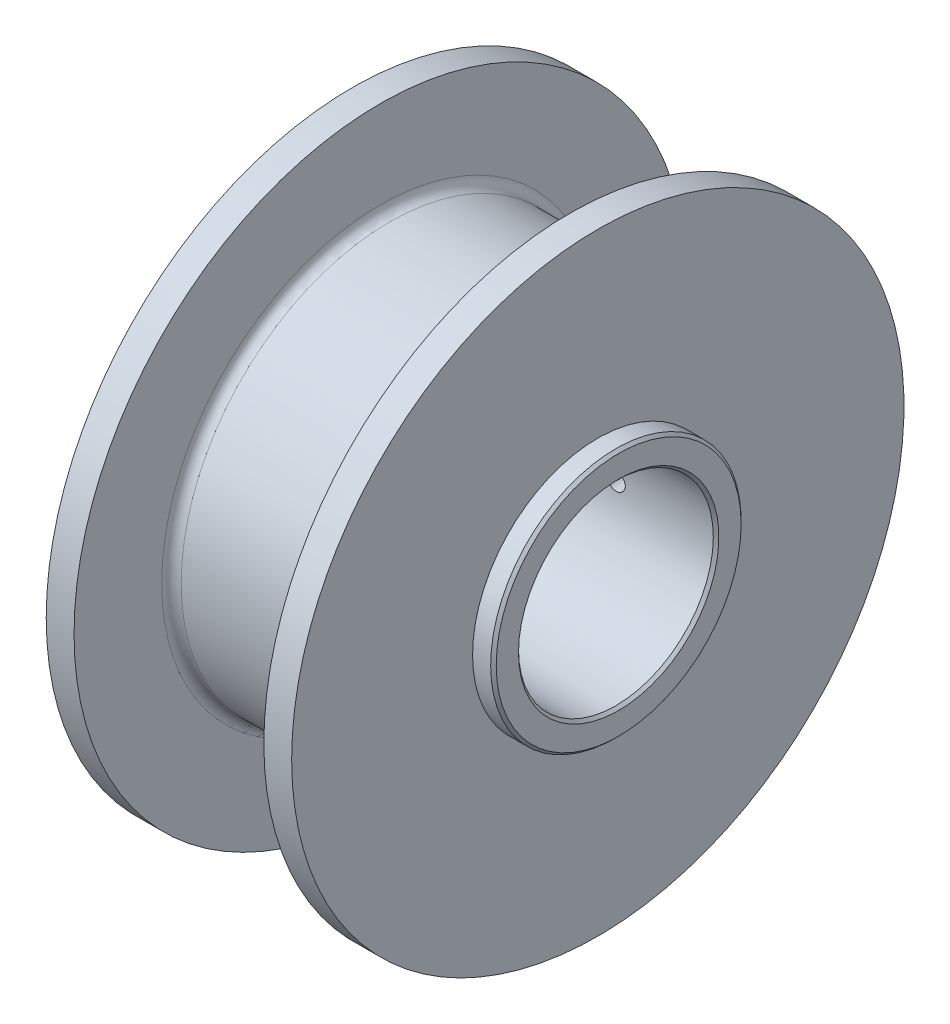
SolidWorks part; units mm, degrees
ref_plane "Front Plane" through (0, 0, 0) normal (0, 0, 1) x (1, 0, 0)
ref_plane "Top Plane" through (0, 0, 0) normal (0, 1, 0) x (1, 0, 0)
ref_plane "Right Plane" through (0, 0, 0) normal (1, 0, 0) x (0, 0, -1)
sketch "Sketch1" plane through (0, 0, 0) normal (0, 0, 1) x (1, 0, 0)
  line L0 (3.81, 55.88) -> (8.89, 55.88)
  line L1 (8.89, 55.88) -> (8.89, 38.1)
  line L3 (43.528, 38.1) -> (43.528, 55.88)
  line L4 (43.528, 55.88) -> (48.608, 55.88)
  line L5 (48.608, 55.88) -> (48.608, 22.86)
  line L6 (48.608, 22.86) -> (52.418, 22.86)
  line L7 (52.418, 22.86) -> (52.418, 17.78)
  line L8 (52.418, 17.78) -> (15.08, 17.78)
  line L9 (15.08, 17.78) -> (15.08, 16.002)
  line L10 (15.08, 16.002) -> (5.08, 16.002)
  line L11 (5.08, 16.002) -> (5.08, 11.08)
  line L12 (5.08, 11.08) -> (0, 11.08)
  line L13 (0, 11.08) -> (0, 22.86)
  line L14 (0, 22.86) -> (3.81, 22.86)
  line L15 (3.81, 22.86) -> (3.81, 55.88)
  line L16 (0, 0) -> (18.9296, 0) construction
  line L18 (8.89, 38.1) -> (43.528, 38.1)
  point P19 (9.4648, 0)
  dimension "D2" = 10
  dimension "D3" = 37.338
  dimension "D1" = 16.002
  dimension "D5" = 17.78
  dimension "D6" = 22.86
  dimension "D7" = 22.86
  dimension "D8" = 5.08
  dimension "D9" = 55.88
  dimension "D10" = 55.88
  dimension "D14" = 3.81
  dimension "D15" = 3.81
  dimension "D16" = 5.08
  dimension "D11" = 38.1
  dimension "D12" = 11.08
revolve "Revolve1" add sketch "Sketch1" angle 360 about L16
ref_plane "Plane1" through (34.257, 0, 0) normal (1, 0, 0) x (0, 0, -1)
sketch "Sketch2" plane through (34.257, 0, 0) normal (1, 0, 0) x (0, 0, -1)
  point P0 (0, 0)
ref_plane "Plane2" through (0, 0, -38.1) normal (0, 0, -1) x (-1, 0, 0)
sketch "Sketch3" plane through (0, 0, -38.1) normal (0, 0, -1) x (-1, 0, 0)
  line L0 (0, 0) -> (-24.097, 0) construction
  line L1 (-44.417, 25.4) -> (-24.097, 25.4)
  line L2 (-44.417, 25.4) -> (-44.417, -25.4)
  line L3 (-44.417, -25.4) -> (-24.097, -25.4)
  line L4 (-24.097, 25.4) -> (-24.097, -25.4)
  line L5 (-34.257, 0) -> (-34.257, 25.4) construction
  point P4 (0, 0)
  point P8 (-34.257, 0)
  dimension "D1" = 50.8
  dimension "D2" = 20.32
extrude "Cut-Extrude1" cut sketch "Sketch3" against normal blind 2.54
sketch "Sketch4" plane through (0, 0, -38.1) normal (0, 0, -1) x (-1, 0, 0)
  point P0 (-34.257, 0)
hole_wizard "1/8 (0.125) Diameter Hole1" positions "Sketch4" profile "Sketch5" hole size "1/8" standard "ANSI Inch" end condition up to next
sketch "Sketch5" plane through (34.257, 0, -38.1) normal (1, 0, 0) x (0, 1, 0)
  line L0 (0, 0) -> (0, 20.32)
  line L1 (0, 20.32) -> (1.5875, 20.32)
  line L2 (1.5875, 20.32) -> (1.5875, 0)
  line L5 (1.5875, 0) -> (0, 0)
  line L11 (0, -6.35) -> (0, 107.95) construction
  dimension "Thru Hole Dia." = 3.175
  dimension "Thru Hole Depth" = 20.32
fillet "Fillet2" radius 1.778 2 edges at (8.89, 0, 38.1) (43.528, 0, 38.1)
chamfer "Chamfer1" distance 0.508 4 edges at (0, 0, 22.86) (52.418, 0, 22.86) (52.418, 0, 17.78) (0, 0, 11.08)
equation "\"bearing_radius\"= 0.629921"
equation "\"bearing_width\"=0.393701"
equation "\"D2@Sketch1\"=\"bearing_width\""
equation "\"kero_radius\"=0.23622in"
equation "\"lox_radius\"=0.23622in"
equation "\"Cavity_width\"=0.031in"
equation "\"tooth_width\"=0.01in"
equation "\"cavity_depth\"=0.031in"
equation "\"seal_step\"=0.01in"
equation "\"purge_length\"=0.04in"
equation "\"insert_radius\" = 0.7in"
equation "\"recycle_groove width\" = 0.06in"
equation "\"recycle_groove_depth\" = 0.06in"
equation "\"N2_purge_width\"= .06in"
equation "\"N2_purge_depth\"= .06in"
equation "\"drain_width\"= .06in"
equation "\"drain_depth\"= .06in"
equation "\"radial_clearance\"= .002in"
equation "\"IPS_flange_width\"= .2in"
equation "\"IPS_flange_radius\" = 2.2in"
equation "\"IPS_LOX_male_radius\"= .9in"
equation "\"IPS_Kero_male_radius\" = .9in"
equation "\"IPS_radius\"= 1.5in"
equation "\"D5@Sketch1\"=\"insert_radius\""
equation "\"InsertLength\"= 1.47in"
equation "\"D3@Sketch1\"=\"InsertLength\""
equation "\"D6@Sketch1\"=\"IPS_Kero_male_radius\""
equation "\"D7@Sketch1\"=\"IPS_LOX_male_radius\""
equation "\"D8@Sketch1\"=\"IPS_flange_width\""
equation "\"D9@Sketch1\"=\"IPS_flange_radius\""
equation "\"D10@Sketch1\"=\"IPS_flange_radius\""
equation "\"D12@Sketch1\"=\"lox_radius\"+.2"
equation "\"D11@Sketch1\"=\"IPS_radius\""
